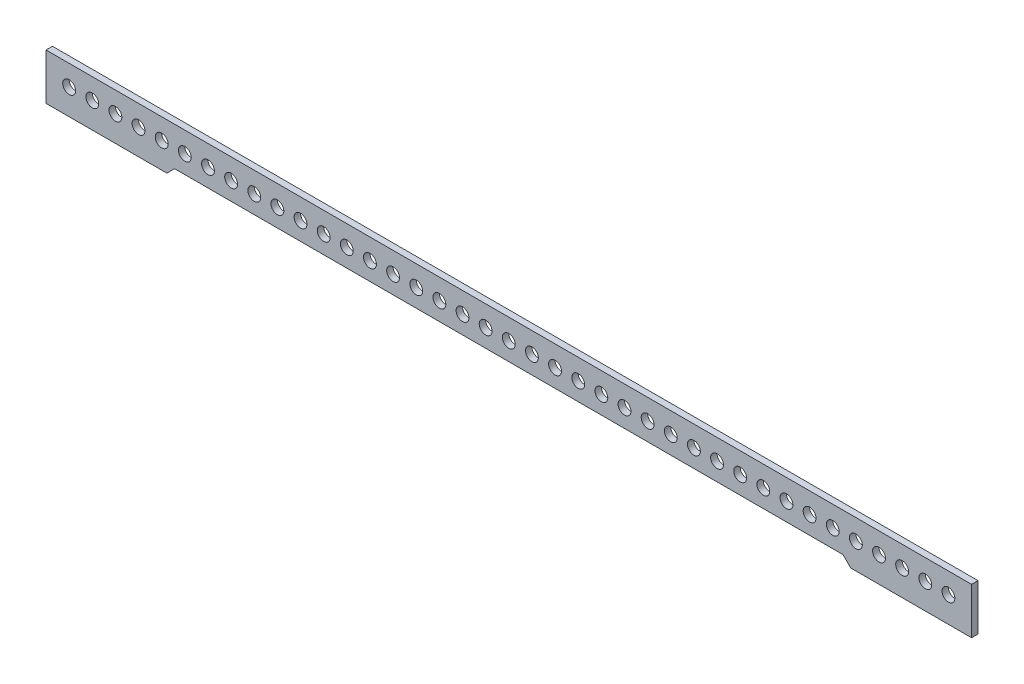
SolidWorks part; units mm, degrees
ref_plane "Front Plane" through (0, 0, 0) normal (0, 0, 1) x (1, 0, 0)
ref_plane "Top Plane" through (0, 0, 0) normal (0, 1, 0) x (1, 0, 0)
ref_plane "Right Plane" through (0, 0, 0) normal (1, 0, 0) x (0, 0, -1)
sketch "Sketch1" plane through (0, 0, 0) normal (0, 0, 1) x (1, 0, 0)
  line L0 (-228.6, 0) -> (228.6, 0)
  line L2 (228.6, -22.86) -> (168.91, -22.86)
  line L3 (168.91, -22.86) -> (165.1, -19.05)
  line L4 (165.1, -19.05) -> (-165.1, -19.05)
  line L5 (-165.1, -19.05) -> (-168.91, -22.86)
  line L6 (-168.91, -22.86) -> (-228.6, -22.86)
  line L8 (-228.6, -22.86) -> (-228.6, 0)
  line L9 (228.6, 0) -> (228.6, -22.86)
  dimension "D1" = 457.2
  dimension "D2" = 22.86
  dimension "D3" = 330.2
  dimension "D4" = 3.81
extrude "Boss-Extrude1" add sketch "Sketch1" along normal blind 3.175
sketch "Sketch3" plane through (0, 0, 3.175) normal (0, 0, 1) x (1, 0, 0)
  line L0 (228.6, 0) -> (-228.6, 0) construction
  line L1 (-217.17, -10.16) -> (-228.6, -10.16) construction
  line L2 (-217.17, -10.16) -> (-205.74, -10.16) construction
  line L3 (217.17, -10.16) -> (228.6, -10.16) construction
  line L4 (-228.6, 0) -> (-228.6, -22.86) construction
  line L5 (228.6, -22.86) -> (228.6, 0) construction
  circle A0 centre (-217.17, -10.16) radius 3.175
  circle A1 centre (-205.74, -10.16) radius 3.175
  circle A2 centre (-194.31, -10.16) radius 3.175
  circle A3 centre (-182.88, -10.16) radius 3.175
  circle A4 centre (-171.45, -10.16) radius 3.175
  circle A5 centre (-160.02, -10.16) radius 3.175
  circle A6 centre (-148.59, -10.16) radius 3.175
  circle A7 centre (-137.16, -10.16) radius 3.175
  circle A8 centre (-125.73, -10.16) radius 3.175
  circle A9 centre (-114.3, -10.16) radius 3.175
  circle A10 centre (-102.87, -10.16) radius 3.175
  circle A11 centre (-91.44, -10.16) radius 3.175
  circle A12 centre (-80.01, -10.16) radius 3.175
  circle A13 centre (-68.58, -10.16) radius 3.175
  circle A14 centre (-57.15, -10.16) radius 3.175
  circle A15 centre (-45.72, -10.16) radius 3.175
  circle A16 centre (-34.29, -10.16) radius 3.175
  circle A17 centre (-22.86, -10.16) radius 3.175
  circle A18 centre (-11.43, -10.16) radius 3.175
  circle A19 centre (0, -10.16) radius 3.175
  circle A20 centre (11.43, -10.16) radius 3.175
  circle A21 centre (22.86, -10.16) radius 3.175
  circle A22 centre (34.29, -10.16) radius 3.175
  circle A23 centre (45.72, -10.16) radius 3.175
  circle A24 centre (57.15, -10.16) radius 3.175
  circle A25 centre (68.58, -10.16) radius 3.175
  circle A26 centre (80.01, -10.16) radius 3.175
  circle A27 centre (91.44, -10.16) radius 3.175
  circle A28 centre (102.87, -10.16) radius 3.175
  circle A29 centre (114.3, -10.16) radius 3.175
  circle A30 centre (125.73, -10.16) radius 3.175
  circle A31 centre (137.16, -10.16) radius 3.175
  circle A32 centre (148.59, -10.16) radius 3.175
  circle A33 centre (160.02, -10.16) radius 3.175
  circle A34 centre (171.45, -10.16) radius 3.175
  circle A35 centre (182.88, -10.16) radius 3.175
  circle A36 centre (194.31, -10.16) radius 3.175
  circle A37 centre (205.74, -10.16) radius 3.175
  circle A38 centre (217.17, -10.16) radius 3.175
  dimension "D1" = 6.35
  dimension "D2" = 10.16
  dimension "D5" = 11.43
  dimension "D4" = 39
extrude "Cut-Extrude2" cut sketch "Sketch3" against normal through all
